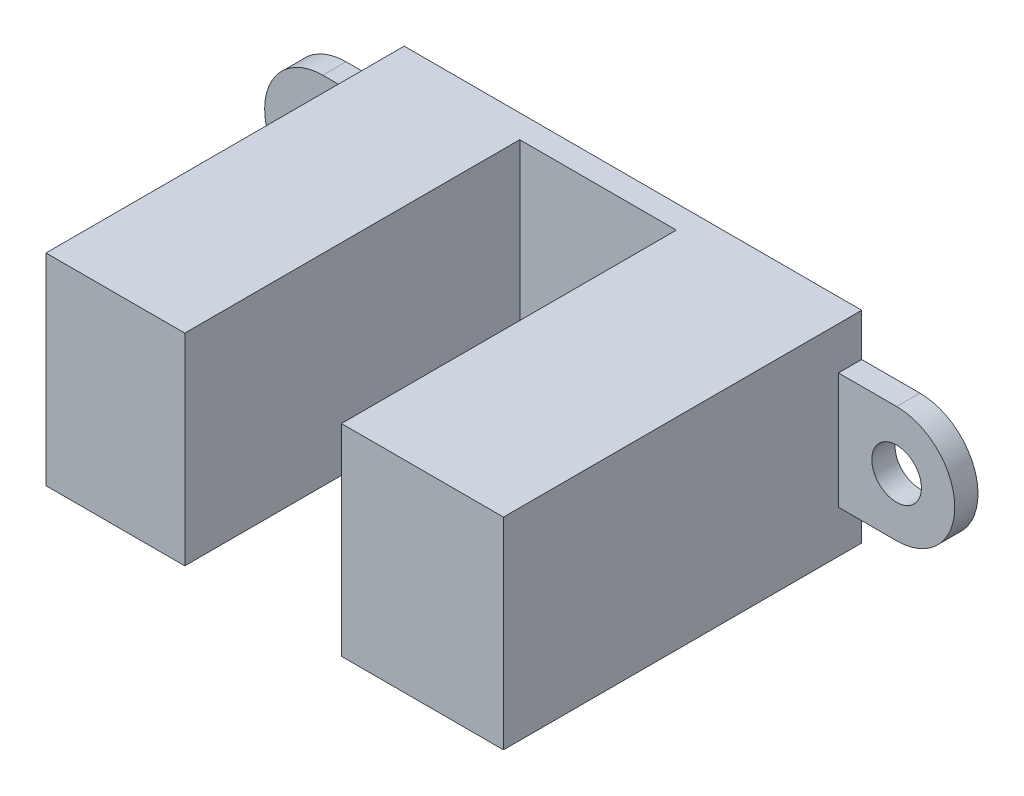
SolidWorks part; units mm, degrees
ref_plane "Front Plane" through (0, 0, 0) normal (0, 0, 1) x (1, 0, 0)
ref_plane "Top Plane" through (0, 0, 0) normal (0, 1, 0) x (1, 0, 0)
ref_plane "Right Plane" through (0, 0, 0) normal (1, 0, 0) x (0, 0, -1)
sketch "Sketch1" plane through (0, 0, 0) normal (0, 0, 1) x (1, 0, 0)
  line L0 (0, 6.5) -> (0, -6.5) construction
  line L1 (-14.75, -6.5) -> (14.75, -6.5)
  line L2 (-14.75, -6.5) -> (-14.75, 6.5)
  line L3 (-14.75, 6.5) -> (14.75, 6.5)
  line L4 (14.75, -6.5) -> (14.75, 6.5)
  line L5 (-14.75, -6.5) -> (14.75, 6.5) construction
  line L6 (-14.75, 6.5) -> (14.75, -6.5) construction
  line L7 (14.75, 3.75) -> (18.5, 3.75)
  line L8 (14.75, 3.75) -> (14.75, -3.75)
  line L9 (14.75, -3.75) -> (18.5, -3.75)
  line L10 (18.5, 3.75) -> (18.5, -3.75)
  line L11 (-14.75, -3.75) -> (-18.5, -3.75)
  line L12 (-18.5, 3.75) -> (-18.5, -3.75)
  line L13 (-14.75, 3.75) -> (-18.5, 3.75)
  line L14 (-14.75, 3.75) -> (-14.75, -3.75)
  circle A0 centre (18.5, 0) radius 3.75
  circle A1 centre (-18.5, 0) radius 3.75
  point P0 (0, 0)
  dimension "D3" = 7.5
  dimension "D1" = 13
  dimension "D2" = 29.5
extrude "Back Plate" add sketch "Sketch1" along normal blind 1.5 contours A1 L12 | L13 A1 L14 | A1 L12 | L2 A1 L11 | L1 L4 L8 L3 L2 L14 | A0 L4 L9 | A0 L7 L8 | L10 A0 | L10 A0 region at (0, 0, 0) region at (-15.5876, -2.9124, 0) region at (15.5876, -2.9124, 0) region at (-15.5876, 2.9124, 0) region at (-16.9085, 0, 0) region at (-20.0915, 0, 0) region at (15.5876, 2.9124, 0) region at (16.9085, 0, 0) region at (20.0915, 0, 0)
sketch "Sketch2" plane through (0, 0, 0) normal (1, 0, 0) x (0, 0, -1)
  line L0 (-1.5, -6.5) -> (0, -6.5) construction
  line L1 (-1.5, 6.5) -> (-23.1, 6.5)
  line L2 (-1.5, 6.5) -> (-1.5, -6.5)
  line L3 (-1.5, -6.5) -> (-23.1, -6.5)
  line L4 (-23.1, 6.5) -> (-23.1, -6.5)
  dimension "D1" = 13
  dimension "D2" = 21.6
extrude "Detector Side" add sketch "Sketch2" against normal blind 10.45 from surface starting at face at (14.75, 5.125, 0.75)
extrude "Emitter Side" add sketch "Sketch2<2>" along normal blind 8.95 from surface starting at face at (-14.75, 5.125, 0.75)
sketch "Sketch2<2>" plane through (0, 0, 0) normal (1, 0, 0) x (0, 0, -1) same geometry as "Sketch2"
hole_wizard "Ø3.2 (3.2) Diameter Hole1" positions "Sketch3" profile "Sketch4" hole size "Ø3.2" standard "ANSI Metric"
sketch "Sketch3" plane through (0, 0, 0) normal (0, 0, -1) x (-1, 0, 0)
  line L0 (-18.5, 3.75) -> (-18.5, -3.75) construction
  line L2 (-22.25, 0) -> (22.25, 0) construction
  line L4 (18.5, 3.75) -> (18.5, -3.75) construction
  arc A0 (-18.5, 3.75) -> (-18.5, -3.75) centre (-18.5, 0) ccw construction
  arc A1 (18.5, -3.75) -> (18.5, 3.75) centre (18.5, 0) ccw construction
  point P0 (-18.5, 0)
  point P2 (18.5, 0)
sketch "Sketch4" plane through (18.5, 0, 0) normal (1, 0, 0) x (0, 1, 0)
  line L0 (0, 0) -> (0, 4.9614)
  line L1 (0, 4.9614) -> (1.6, 4)
  line L2 (1.6, 4) -> (1.6, 0)
  line L5 (1.6, 0) -> (0, 0)
  line L10 (0, 4.9614) -> (-1.6, 4) construction
  line L11 (0, -6.35) -> (0, 107.95) construction
  dimension "Hole Dia." = 3.2
  dimension "Hole Depth" = 4
  dimension "Drill Angle" = 118
